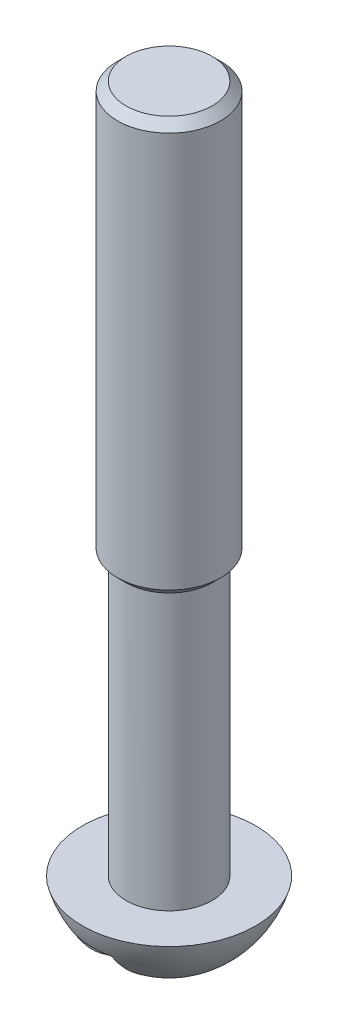
SolidWorks part; units mm, degrees
material "Plain Carbon Steel"
ref_plane "Спереди" through (0, 0, 0) normal (0, 0, 1) x (1, 0, 0)
ref_plane "Сверху" through (0, 0, 0) normal (0, 1, 0) x (1, 0, 0)
ref_plane "Справа" through (0, 0, 0) normal (1, 0, 0) x (0, 0, -1)
sketch "Sketch1" plane through (0, 0, 0) normal (0, 1, 0) x (1, 0, 0)
  circle A0 centre (0, 0) radius 1.5
  dimension "D1" = 3
extrude "Boss-Extrude1" add sketch "Sketch1" along normal blind 20
sketch "Sketch2" plane through (0, 0, 0) normal (0, 0, 1) x (1, 0, 0)
  line L0 (0, 0) -> (-2.52, 0)
  line L1 (0, -2.1) -> (0, 0) construction
  line L2 (0, 0) -> (0, -2.1)
  arc A0 (-2.52, 0) -> (0, -2.1) centre (0.2711, 0.7873) ccw
  dimension "D3" = 2.9
  dimension "D1" = 2.52
  dimension "D2" = 2.1
revolve "Revolve1" add sketch "Sketch2" angle 360 about L1
sketch "Sketch3" plane through (0, 0, 0) normal (0, 0, 1) x (1, 0, 0)
  line L0 (-0.5, -0.7) -> (0, -0.7)
  line L1 (0, -0.7) -> (0.5, -0.7)
  line L2 (0.5, -0.7) -> (0.5, -4.6381)
  line L3 (0.5, -4.6381) -> (-0.5, -4.6381)
  line L4 (-0.5, -4.6381) -> (-0.5, -0.7)
  dimension "D1" = 0.7
  dimension "D2" = 1
extrude "Cut-Extrude1" cut sketch "Sketch3" against normal through all and the other way through all
sketch "Sketch4" plane through (0, 0, 0) normal (0, 1, 0) x (1, 0, 0)
  circle A0 centre (0, 0) radius 1.25
  circle A1 centre (0, 0) radius 2.52
  dimension "D1" = 2.5
extrude "Cut-Extrude2" cut sketch "Sketch4" along normal blind 8
chamfer "Chamfer1" distance 0.25 angle 45 2 edges at (0, 20, 1.5) (-1.5, 8, 0)
